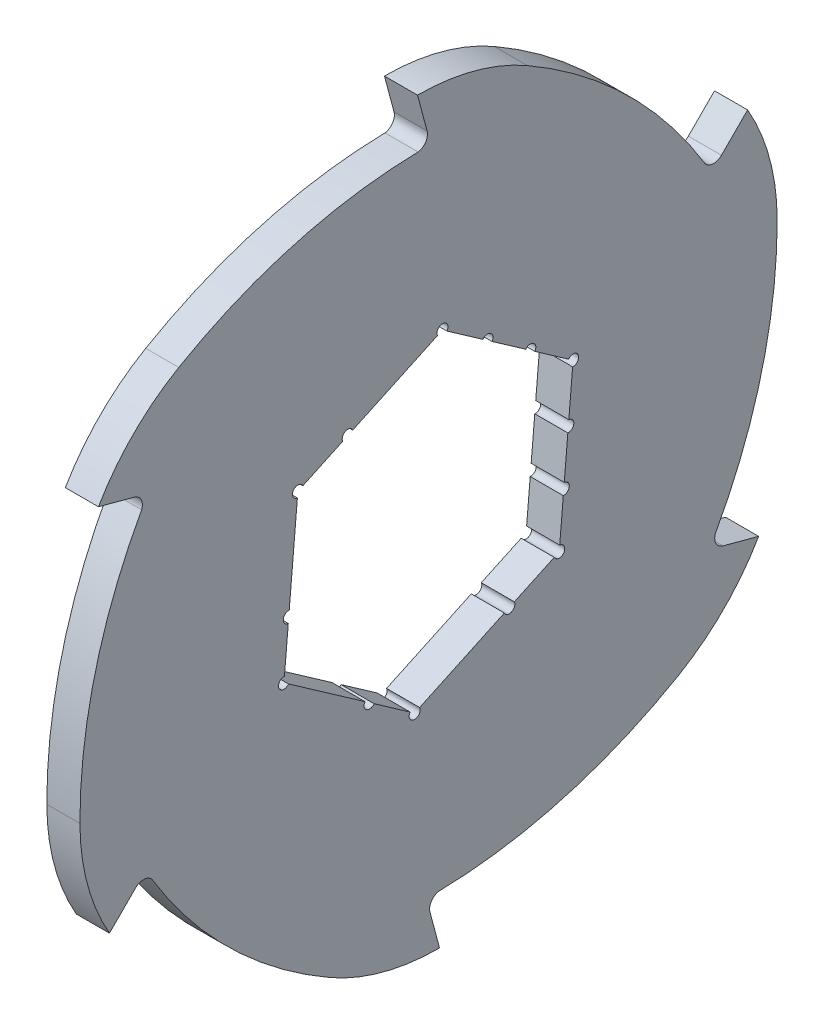
SolidWorks part; units mm, degrees
note: '?' marks a value the reader was unsure of.
material "1.0037 (S235JR)"
ref_plane "Alzado" through (0, 0, 0) normal (0, 0, 1) x (1, 0, 0)
ref_plane "Planta" through (0, 0, 0) normal (0, 1, 0) x (1, 0, 0)
ref_plane "Vista lateral" through (0, 0, 0) normal (1, 0, 0) x (0, 0, -1)
sketch "Sketch1" plane through (0, 0, 0) normal (1, 0, 0) x (0, 0, -1)
  line L0 (-56.6126, 0) -> (65.57, 0) construction
  line L1 (26.2152, 12.2243) -> (2.521, 28.8152)
  line L2 (2.521, 28.8152) -> (-23.6942, 16.5908)
  line L3 (-23.6942, 16.5908) -> (-26.2152, -12.2243)
  line L4 (-26.2152, -12.2243) -> (-2.521, -28.8152)
  line L5 (-2.521, -28.8152) -> (23.6942, -16.5908)
  line L6 (23.6942, -16.5908) -> (26.2152, 12.2243)
  circle A0 centre (0, 0) radius 25.05 construction
  circle A1 centre (0, 0) radius 59
  dimension "D2" = 118
  dimension "D1" = 50.1
  dimension "D3" = 35
extrude "Extrude1" add sketch "Sketch1" along normal mid plane 6
ref_axis "Axis1" through (-5.5, 0, 0) along (1, 0, 0)?
sketch "Sketch2" plane through (0, 0, 0) normal (1, 0, 0) x (0, 0, -1)
  line L0 (-2, 67.9618) -> (-0.2627, 61.4781)
  line L1 (0, 0) -> (0, 77.6328) construction
  line L4 (-2.1226, 58.9618) -> (0, 0) construction
  circle A0 centre (0, 0) radius 59 construction
  arc A1 (-2, 67.9618) -> (17.9271, 62.6448) centre (-2, 27.9618) cw
  arc A3 (51.2137, 29.2943) -> (-2.1226, 58.9618) centre (0, 0) ccw
  arc A4 (-0.2627, 61.4781) -> (-2.1226, 58.9618) centre (-2.1946, 60.9605) cw
  arc A5 (17.9271, 62.6448) -> (51.2137, 29.2943) centre (-26.9089, -15.3919) cw
  point P10 (-2, 67.9618)
  dimension "D2" = 40
  dimension "D4" = 2
  dimension "D3" = 9
  dimension "D6" = 90
  dimension "D1" = 15
  dimension "D5" = 2
extrude "Extrude2" add sketch "Sketch2" against normal mid plane 6
fillet "Fillet1" [suppressed] radius 0.6
pattern_circular "CirPattern1" count 6 over 360 about axis through (0, 0, 0) along (1, 0, 0) of "Extrude2", "Fillet1"
sketch "Sketch4" [suppressed] plane through (3, 0, 0) normal (1, 0, 0) x (0, 0, -1)
  circle A0 centre (0, 0) radius 67.9646 construction
  dimension "D1" = 135.9291
hole_wizard "Ø2.0 (2) Diameter Hole1" positions "Sketch5" profile "Sketch7" hole size "Ø2.0" standard "ISO" end condition up to next
sketch "Sketch5" plane through (3, 0, 0) normal (1, 0, 0) x (0, 0, -1)
  point P0 (2.521, 28.8152)
  point P7 (26.2152, 12.2243)
  point P8 (23.6942, -16.5908)
  point P9 (-2.521, -28.8152)
  point P10 (-26.2152, -12.2243)
  point P11 (-23.6942, 16.5908)
  dimension "D1" = 6
sketch "Sketch7" plane through (3, 28.8152, -2.521) normal (0, 1, 0) x (0, 0, -1)
  line L0 (0, 0) -> (0, 6)
  line L1 (0, 6) -> (1, 6)
  line L2 (1, 6) -> (1, 0)
  line L5 (1, 0) -> (0, 0)
  line L11 (0, -6.35) -> (0, 107.95) construction
  dimension "Diámetro de taladro hasta el siguiente" = 2
  dimension "Profundidad de taladro hasta el siguiente" = 6
hole_wizard "Ø2.0 (2) Diameter Hole3" positions "Sketch10" profile "Sketch11" hole size "Ø2.0" standard "ISO" end condition up to next
sketch "Sketch10" plane through (3, 0, 0) normal (1, 0, 0) x (0, 0, -1)
  line L0 (3.3402, 28.2416) -> (10.6921, 23.0937) construction
  line L1 (25.396, 12.7979) -> (3.3402, 28.2416) construction
  line L2 (10.6921, 23.0937) -> (18.0441, 17.9458) construction
  line L3 (18.0441, 17.9458) -> (25.396, 12.7979) construction
  point P2 (10.6921, 23.0937)
sketch "Sketch11" plane through (3, 23.0937, -10.6921) normal (0, 1, 0) x (0, 0, -1)
  line L0 (0, 0) -> (0, 6.001)
  line L1 (0, 6.001) -> (1, 6.001)
  line L2 (1, 6.001) -> (1, 0)
  line L5 (1, 0) -> (0, 0)
  line L11 (0, -6.35) -> (0, 107.95) construction
  dimension "Diámetro de taladro hasta el siguiente" = 2
  dimension "Profundidad de taladro hasta el siguiente" = 6.001
hole_wizard "Ø2.0 (2) Diameter Hole4" positions "Sketch12" profile "Sketch13" hole size "Ø2.0" standard "ISO" end condition up to next
sketch "Sketch12" plane through (3, 0, 0) normal (1, 0, 0) x (0, 0, -1)
  line L0 (25.396, 12.7979) -> (11.5113, 22.5201) construction
  point P0 (18.4536, 17.659)
sketch "Sketch13" plane through (3, 17.659, -18.4536) normal (0, 1, 0) x (0, 0, -1)
  line L0 (0, 0) -> (0, 6.001)
  line L1 (0, 6.001) -> (1, 6.001)
  line L2 (1, 6.001) -> (1, 0)
  line L5 (1, 0) -> (0, 0)
  line L11 (0, -6.35) -> (0, 107.95) construction
  dimension "Diámetro de taladro hasta el siguiente" = 2
  dimension "Profundidad de taladro hasta el siguiente" = 6.001
pattern_circular "CirPattern2" count 6 every 60 about axis through (0, 0, 0) along (1, 0, 0) of "Ø2.0 (2) Diameter Hole3"
pattern_circular "CirPattern3" count 2 every 60 about axis through (-5.5, 0, 0) along (1, 0, 0) of "Ø2.0 (2) Diameter Hole4"
equation "\"D1@Extrude2\"=\"D1@Extrude1\""
